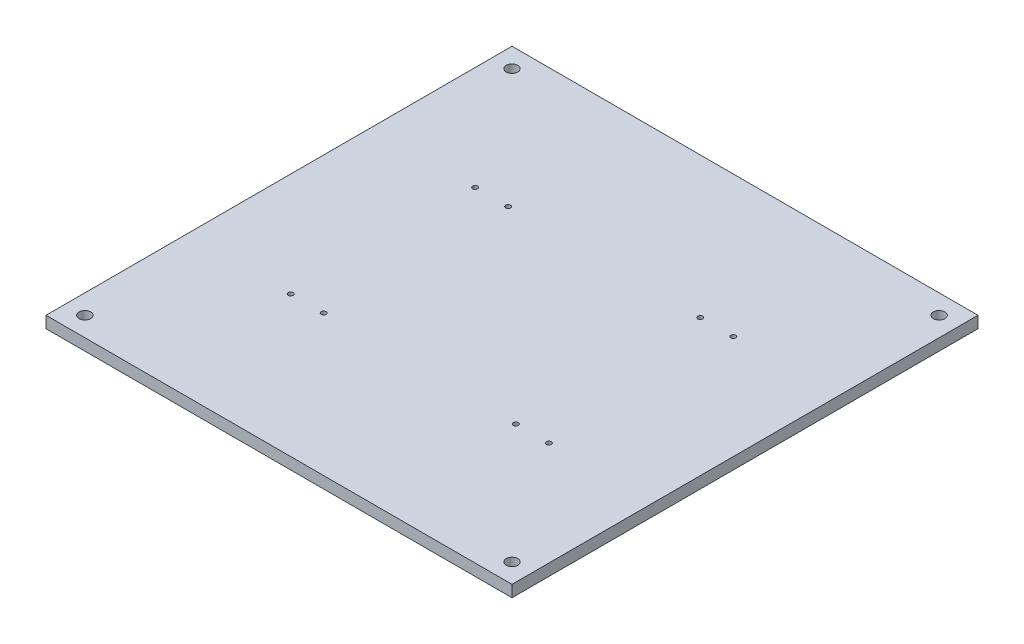
SolidWorks part; units mm, degrees
material "PMMA"
ref_plane "前视基准面" through (0, 0, 0) normal (0, 0, 1) x (1, 0, 0)
ref_plane "上视基准面" through (0, 0, 0) normal (0, 1, 0) x (1, 0, 0)
ref_plane "右视基准面" through (0, 0, 0) normal (1, 0, 0) x (0, 0, -1)
sketch "草图1" plane through (0, 0, 0) normal (0, 1, 0) x (1, 0, 0)
  line L0 (-120, 118) -> (-120, 120)
  line L1 (-118, -120) -> (118, -120)
  line L2 (-120, -118) -> (-120, 118)
  line L3 (-118, 120) -> (118, 120)
  line L4 (120, -118) -> (120, 118)
  line L5 (-120, -120) -> (120, 120) construction
  line L6 (-120, 120) -> (120, -120) construction
  line L7 (-120, 120) -> (-118, 120)
  line L8 (118, 120) -> (120, 120)
  line L9 (120, 120) -> (120, 118)
  line L10 (120, -118) -> (120, -120)
  line L11 (120, -120) -> (118, -120)
  line L12 (-120, -118) -> (-120, -120)
  line L13 (-120, -120) -> (-118, -120)
  point P0 (0, 0)
  dimension "D1" = 240
  dimension "D2" = 240
extrude "凸台-拉伸1" add sketch "草图1" against normal blind 6
sketch "Sketch2" plane through (0, -6, 0) normal (0, -1, 0) x (1, 0, 0)
  line L0 (0, -120) -> (0, 165.2098) construction
  line L1 (120, -120) -> (-120, -120) construction
  line L2 (-120, 0) -> (120, 0) construction
  line L3 (-120, -120) -> (-120, 120) construction
  line L4 (120, 120) -> (120, -120) construction
  line L5 (-66.5, -47.5) -> (-66.5, 47.5) construction
  line L6 (-66.5, 47.5) -> (-49.5, 47.5) construction
  line L7 (-49.5, 47.5) -> (-49.5, -47.5) construction
  line L8 (-66.5, -47.5) -> (-49.5, -47.5) construction
  line L9 (66.5, -47.5) -> (49.5, -47.5) construction
  line L10 (49.5, 47.5) -> (49.5, -47.5) construction
  line L11 (66.5, 47.5) -> (49.5, 47.5) construction
  line L12 (66.5, -47.5) -> (66.5, 47.5) construction
  line L13 (-120, 120) -> (120, 120) construction
  circle A0 centre (-66.5, 47.5) radius 1.25
  circle A1 centre (-49.5, 47.5) radius 1.25
  circle A2 centre (-66.5, -47.5) radius 1.25
  circle A3 centre (-49.5, -47.5) radius 1.25
  circle A4 centre (49.5, -47.5) radius 1.25
  circle A5 centre (66.5, -47.5) radius 1.25
  circle A6 centre (49.5, 47.5) radius 1.25
  circle A7 centre (66.5, 47.5) radius 1.25
  circle A8 centre (-110, 110) radius 3
  circle A9 centre (110, 110) radius 3
  circle A10 centre (-110, -110) radius 3
  circle A11 centre (110, -110) radius 3
  point P16 (-49.5, 0)
  point P17 (-66.5, 0)
  point P29 (66.5, 0)
  point P30 (49.5, 0)
  dimension "D4" = 2.5
  dimension "D5" = 2.5
  dimension "D6" = 2.5
  dimension "D7" = 2.5
  dimension "D8" = 6
  dimension "D1" = 47.5
  dimension "D2" = 17
  dimension "D3" = 66.5
  dimension "D9" = 10
  dimension "D10" = 10
extrude "Cut-Extrude1" cut sketch "Sketch2" against normal through all
cosmetic thread "Cosmetic Thread1"
cosmetic thread "Cosmetic Thread2"
cosmetic thread "Cosmetic Thread3"
cosmetic thread "Cosmetic Thread4"
cosmetic thread "Cosmetic Thread5"
cosmetic thread "Cosmetic Thread6"
cosmetic thread "Cosmetic Thread7"
cosmetic thread "Cosmetic Thread8"
